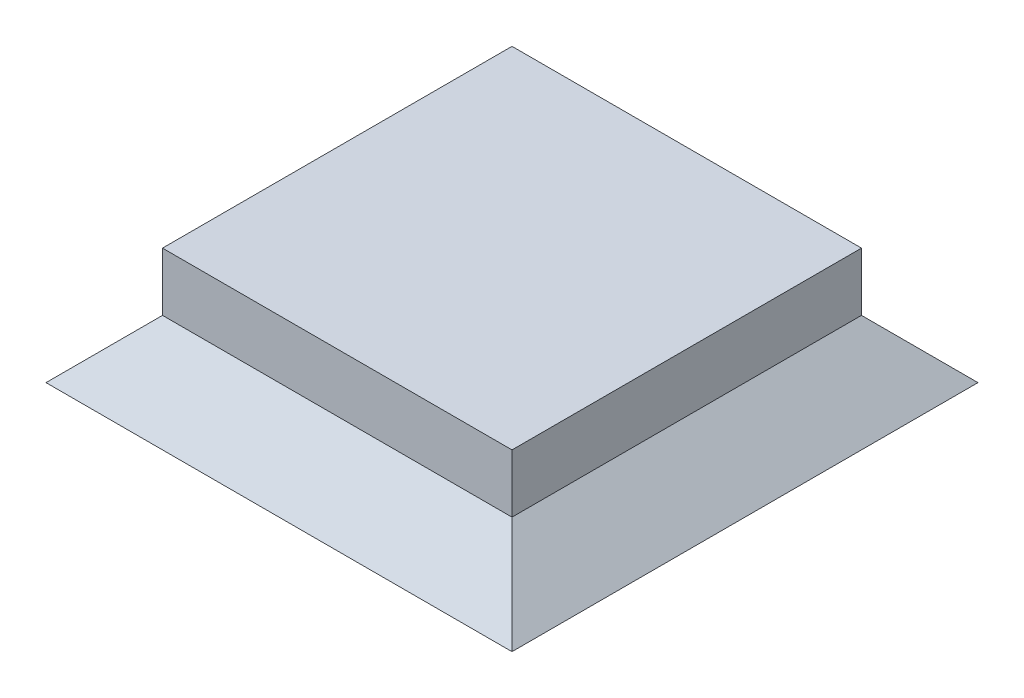
SolidWorks part; units mm, degrees
ref_plane "前视基准面" through (0, 0, 0) normal (0, 0, 1) x (1, 0, 0)
ref_plane "上视基准面" through (0, 0, 0) normal (0, 1, 0) x (1, 0, 0)
ref_plane "右视基准面" through (0, 0, 0) normal (1, 0, 0) x (0, 0, -1)
sketch "草图1" plane through (0, 0, 0) normal (0, 1, 0) x (1, 0, 0)
  line L1 (-3, 3) -> (3, 3)
  line L2 (-3, 3) -> (-3, -3)
  line L3 (-3, -3) -> (3, -3)
  line L4 (3, 3) -> (3, -3)
  line L5 (-3, 3) -> (3, -3) construction
  line L6 (-3, -3) -> (3, 3) construction
  point P0 (0, 0)
  dimension "D1" = 6
  dimension "D2" = 6
extrude "凸台-拉伸1" add sketch "草图1" along normal blind 2
sketch "草图3" plane through (0, 0, 0) normal (0, 1, 0) x (1, 0, 0)
  line L0 (3, -3) -> (3, 3) construction
  line L1 (-4, 4) -> (4, 4)
  line L2 (-4, 4) -> (-4, -4)
  line L3 (-4, -4) -> (4, -4)
  line L4 (4, 4) -> (4, -4)
  line L5 (-4, 4) -> (4, -4) construction
  line L6 (-4, -4) -> (4, 4) construction
  line L7 (-3, -3) -> (3, -3) construction
  point P0 (0, 0)
  dimension "D1" = 1
  dimension "D2" = 1
extrude "凸台-拉伸2" add sketch "草图3" along normal blind 1
chamfer "倒角1" distance 1 angle 45 4 edges at (0, 1, -4) (4, 1, 0) (0, 1, 4) (-4, 1, 0)
